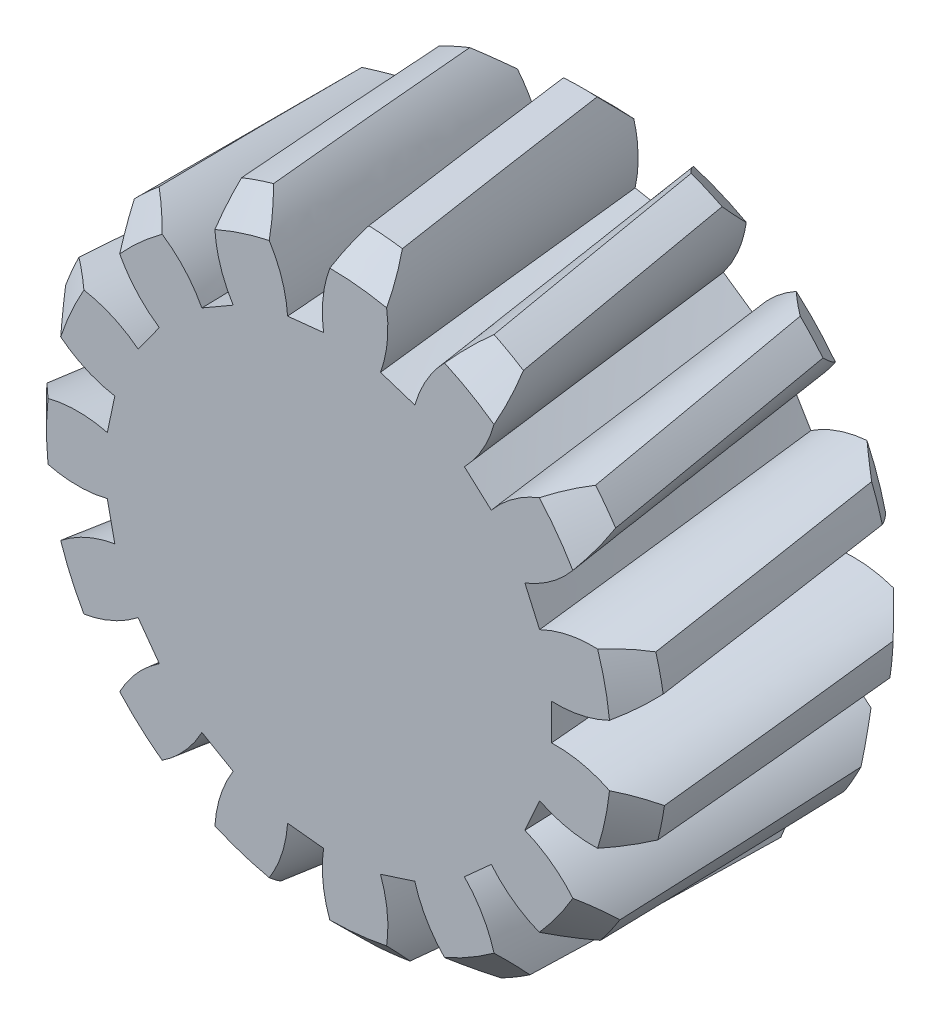
SolidWorks part; units mm, degrees
ref_plane "Front Plane" through (0, 0, 0) normal (1, 0, 0) x (0, 1, 0)
ref_plane "Top Plane" through (0, 0, 0) normal (0, 0, 1) x (0, 1, 0)
ref_plane "Right Plane" through (0, 0, 0) normal (0, 1, 0) x (-1, 0, 0)
sketch "Sketch5" plane through (0, 0, 0) normal (0, 0, 1) x (0, 1, 0)
  circle A0 centre (0, 0) radius 11
  dimension "D1" = 22
extrude "Boss-Extrude1" add sketch "Sketch5" along normal blind 10
chamfer "Chamfer1" distance 1 angle 45 2 edges at (11, 0, 10) (11, 0, 0)
sketch "Sketch9" plane through (0, 0, 10) normal (0, 0, 1) x (1, 0, 0)
  circle A0 centre (0, 0) radius 11 construction
  circle A1 centre (0, 0) radius 11
curve "Helix/Spiral1" pitch 500 height 20 radius 11 left hand yes centre (0, 0, 10) axis (0, 0, -1) start towards (-1, 0, 0)
sketch "Sketch10" plane through (0, 0, 10) normal (0, 0, 1) x (1, 0, 0)
  line L0 (0, 0) -> (31, 0) construction
  line L1 (7.8878, 0.64) -> (7.8878, -0.64)
  circle A0 centre (0, 0) radius 11 construction
  arc A1 (10.8678, -1.7) -> (10.8678, 1.7) centre (0, 0) ccw
  arc A2 (7.8878, 0.64) -> (10.8678, 1.7) centre (8.0522, 4.8968) ccw
  arc A3 (7.8878, -0.64) -> (10.8678, -1.7) centre (8.0522, -4.8968) cw
  point P9 (7.8878, 0)
  dimension "D2" = 3.4
  dimension "D4" = 4.26
  dimension "D1" = 1.28
  dimension "D3" = 2.98
sweep "Cut-Sweep1" cut profiles "Sketch10" path "Helix/Spiral1" align with end faces yes
pattern_circular "CirPattern1" count 15 over 360 about axis through (0, 0, 10) along (0, 0, -1) of "Cut-Sweep1" reverse direction yes
sketch "Sketch11" plane through (0, 0, 0) normal (0, 0, 1) x (0, 1, 0)
  circle A0 centre (0, 0) radius 2.95
  dimension "D1" = 5.9
extrude "Cut-Extrude1" cut sketch "Sketch11" along normal blind 2.75
